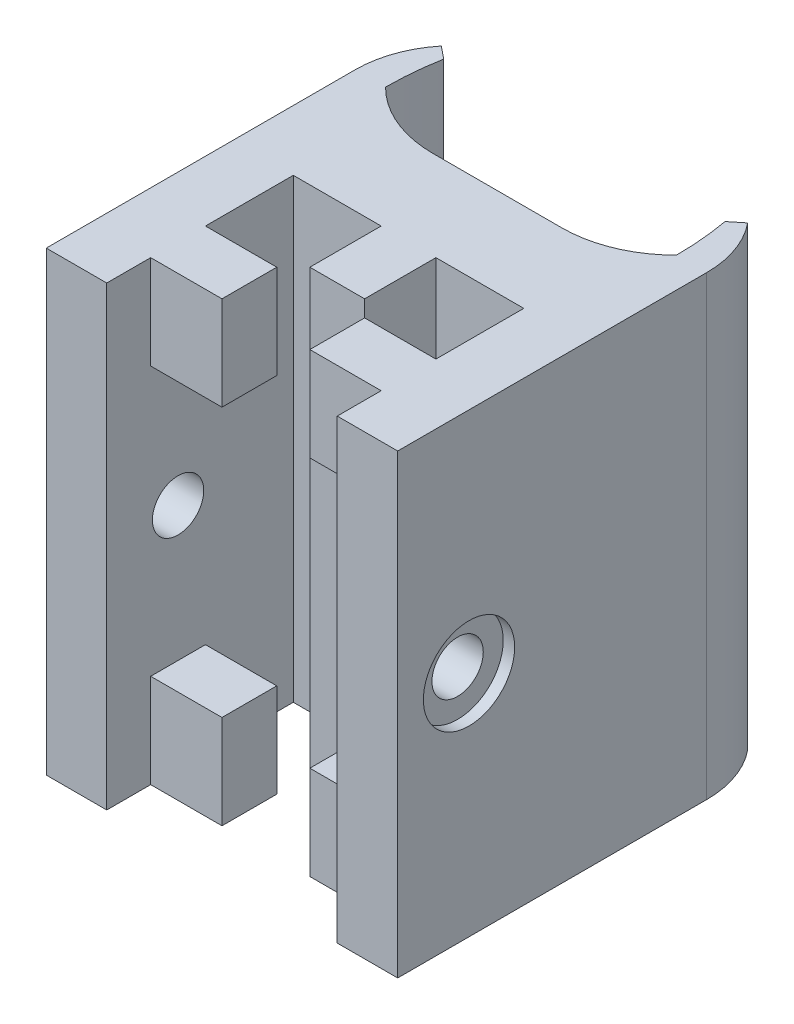
SolidWorks part; units mm, degrees
ref_plane "Plan de face" through (0, 0, 0) normal (0, 0, 1) x (1, 0, 0)
ref_plane "Plan de dessus" through (0, 0, 0) normal (0, 1, 0) x (1, 0, 0)
ref_plane "Plan de droite" through (0, 0, 0) normal (1, 0, 0) x (0, 0, -1)
sketch "Base" plane through (0, 0, 0) normal (0, 1, 0) x (1, 0, 0)
  line L0 (-3.85, -2.4) -> (-3.85, 2.4)
  line L1 (-3.85, 2.4) -> (-10.1, 2.4)
  line L2 (-10.1, 2.4) -> (-10.1, 10.1)
  line L3 (-10.1, 10.1) -> (-2.4, 10.1)
  line L4 (-2.4, 10.1) -> (-2.4, 3.85)
  line L5 (-2.4, 3.85) -> (2.4, 3.85)
  line L6 (0, -55) -> (0, 55) construction
  line L7 (2.4, 10.1) -> (2.4, 3.85)
  line L8 (10.1, 10.1) -> (2.4, 10.1)
  line L9 (10.1, 2.4) -> (10.1, 10.1)
  line L10 (3.85, 2.4) -> (10.1, 2.4)
  line L11 (3.85, -2.4) -> (3.85, 2.4)
  line L12 (-55, 0) -> (55, 0) construction
  line L13 (3.85, -2.4) -> (10.1, -2.4)
  line L14 (10.1, -2.4) -> (10.1, -6.25)
  line L20 (-10.1, -2.4) -> (-10.1, -6.25)
  line L21 (-3.85, -2.4) -> (-10.1, -2.4)
  line L23 (-15.4, 15.4) -> (15.4, 15.4)
  line L24 (-15.4, 15.4) -> (-15.4, -6.25)
  line L26 (15.4, 15.4) -> (15.4, -6.25)
  line L27 (-15.4, 15.4) -> (0, 0) construction
  line L28 (0, 0) -> (15.4, 15.4) construction
  line L29 (-10.1, -6.25) -> (-15.4, -6.25)
  line L30 (10.1, -6.25) -> (15.4, -6.25)
  line L31 (10.1, -10.1) -> (15.4, -15.4) construction
  point P2 (-3.85, 0)
  point P3 (0, 3.85)
  point P27 (0, 0)
  dimension "D1" = 4.8
  dimension "D2" = 4.8
  dimension "D3" = 6.25
  dimension "D4" = 7.7
  dimension "D5" = 30.8
extrude "Boss.-Extru.1" add sketch "Base" along normal mid plane 40
hole_wizard "Chambrage pour vis à six pans creux M41" positions "Esquisse4" profile "Esquisse5" counterbore size "M4" standard "ISO" end condition up to next
sketch "Esquisse4" plane through (15.4, 0, 0) normal (1, 0, 0) x (0, 0, -1)
  point P0 (0, 0)
sketch "Esquisse5" plane through (15.4, 0, 0) normal (0, 1, 0) x (0, 0, -1)
  line L0 (0, 0) -> (0, 11.55)
  line L1 (0, 11.55) -> (2.25, 11.55)
  line L3 (2.25, 11.55) -> (2.25, 1)
  line L4 (2.25, 1) -> (4, 1)
  line L5 (4, 1) -> (4, 0)
  line L7 (4, 0) -> (0, 0)
  line L11 (0, -6.35) -> (0, 107.95) construction
  dimension "Diamètre du perçage jusqu'au prochain" = 4.5
  dimension "Profondeur du perçage jusqu'au prochain" = 11.55
  dimension "Diamètre du chambrage" = 8
  dimension "Profondeur du chambrage" = 1
mirror "Symétrie1" about plane through (0, 0, 0) normal (1, 0, 0) of "Chambrage pour vis à six pans creux M41"
sketch "Esquisse6" plane through (0, 0, 0) normal (0, 0, 1) x (1, 0, 0)
  line L0 (10.1, 20) -> (10.1, -20) construction
  line L1 (-10.1, 11.7753) -> (10.1, 11.7753)
  line L2 (-10.1, 11.7753) -> (-10.1, -11.7753)
  line L3 (-10.1, -11.7753) -> (10.1, -11.7753)
  line L4 (10.1, 11.7753) -> (10.1, -11.7753)
  line L5 (-10.1, 11.7753) -> (10.1, -11.7753) construction
  line L6 (-10.1, -11.7753) -> (10.1, 11.7753) construction
  point P0 (0, 0)
extrude "Enlèv. mat.-Extru.1" cut sketch "Esquisse6" against normal mid plane 6
sketch "Esquisse7" plane through (0, 0, -10.1) normal (0, 0, 1) x (1, 0, 0)
  line L1 (-6.7175, 6.7175) -> (6.7175, 6.7175) construction
  line L2 (-6.7175, 6.7175) -> (-6.7175, -6.7175) construction
  line L3 (-6.7175, -6.7175) -> (6.7175, -6.7175) construction
  line L4 (6.7175, 6.7175) -> (6.7175, -6.7175) construction
  line L5 (-6.7175, 6.7175) -> (6.7175, -6.7175) construction
  line L6 (-6.7175, -6.7175) -> (6.7175, 6.7175) construction
  circle A0 centre (0, 0) radius 9.5 construction
  dimension "D1" = 19
sketch "Esquisse14" plane through (0, -20, 0) normal (0, -1, 0) x (1, 0, 0)
  line L0 (15.4, 6.25) -> (15.4, -15.4) construction
  line L1 (-15.4, -15.4) -> (15.4, -15.4)
  line L2 (-15.4, -15.4) -> (-15.4, -17.9)
  line L3 (-12.75, -17.8776) -> (12.75, -17.8776)
  line L4 (15.4, -15.4) -> (15.4, -17.9)
  line L5 (-15.4, -17.9) -> (-15.4, -20.8352)
  line L6 (-13.4269, -26.3999) -> (-12.3296, -25.5099)
  line L9 (0, -17.8776) -> (0, -31.0659) construction
  line L10 (-12.75, -17.8776) -> (-12.75, -20.8352)
  line L13 (12.75, -17.8776) -> (12.75, -20.8352)
  line L14 (13.4269, -26.3999) -> (12.3296, -25.5099)
  line L15 (15.4, -17.9) -> (15.4, -20.8352)
  arc A0 (-15.4, -20.8352) -> (-13.4269, -26.3999) centre (-6.5664, -20.8352) ccw
  arc A1 (-12.75, -20.8352) -> (-12.3296, -25.5099) centre (13.4519, -20.8352) ccw
  arc A2 (12.75, -20.8352) -> (12.3296, -25.5099) centre (-13.4519, -20.8352) cw
  arc A3 (15.4, -20.8352) -> (13.4269, -26.3999) centre (6.5664, -20.8352) cw
  point P10 (0, 0)
  point P27 (12.3296, -17.9168)
  dimension "D1" = 2.5
  dimension "D2" = 25.5
extrude "Boss.-Extru.3" add sketch "Esquisse14" against normal up to vertex (40 mm away) up to point (-15.4, 20, -15.4)
fillet "Congé1" radius 10 2 edges at (-12.75, 0, -17.8776) (12.75, 0, -17.8776)
hole_wizard "Chambrage pour vis à six pans creux M31" positions "Esquisse10" profile "Esquisse12" counterbore size "M3" standard "ISO"
sketch "Esquisse10" plane through (0, 0, -10.1) normal (0, 0, 1) x (1, 0, 0)
  point P0 (-6.7175, 6.7175)
  point P3 (-6.7175, -6.7175)
  point P7 (6.7175, 6.7175)
  point P10 (6.7175, -6.7175)
sketch "Esquisse12" plane through (-6.7175, 6.7175, -10.1) normal (1, 0, 0) x (0, -1, 0)
  line L0 (0, 0) -> (0, 7.8)
  line L1 (0, 7.8) -> (1.7, 7.8)
  line L3 (1.7, 7.8) -> (1.7, 3.4)
  line L4 (1.7, 3.4) -> (3.25, 3.4)
  line L5 (3.25, 3.4) -> (3.25, 0)
  line L7 (3.25, 0) -> (0, 0)
  line L11 (0, -6.35) -> (0, 107.95) construction
  dimension "Diamètre du perçage jusqu'au prochain" = 3.4
  dimension "Profondeur du perçage jusqu'au prochain" = 7.8
  dimension "Diamètre du chambrage" = 6.5
  dimension "Profondeur du chambrage" = 3.4
